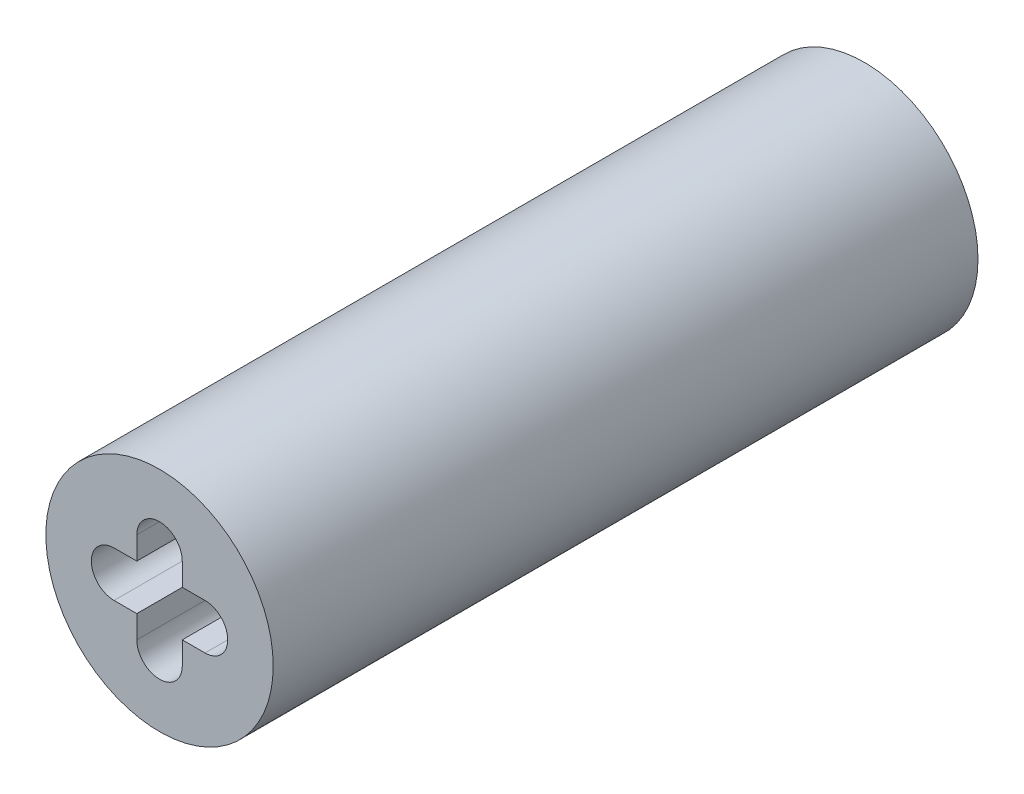
SolidWorks part; units mm, degrees
material "PVC Rigid"
ref_plane "Front Plane" through (0, 0, 0) normal (0, 0, 1) x (1, 0, 0)
ref_plane "Top Plane" through (0, 0, 0) normal (0, 1, 0) x (1, 0, 0)
ref_plane "Right Plane" through (0, 0, 0) normal (1, 0, 0) x (0, 0, -1)
sketch "Sketch1" plane through (0, 0, 0) normal (0, 0, 1) x (1, 0, 0)
  line L0 (0, 0) -> (3.048, 0) construction
  line L1 (0, 0.762) -> (3.048, 0.762)
  line L2 (0, -0.762) -> (3.048, -0.762)
  line L8 (1.524, 1.524) -> (1.524, -1.524) construction
  line L9 (2.286, 1.524) -> (2.286, -1.524)
  line L10 (0.762, 1.524) -> (0.762, -1.524)
  arc A0 (0, 0.762) -> (0, -0.762) centre (0, 0) ccw
  arc A2 (3.048, -0.762) -> (3.048, 0.762) centre (3.048, 0) ccw
  arc A4 (2.286, 1.524) -> (0.762, 1.524) centre (1.524, 1.524) ccw
  arc A5 (0.762, -1.524) -> (2.286, -1.524) centre (1.524, -1.524) ccw
  circle A7 centre (1.524, 0) radius 2.286 construction
  circle A8 centre (1.524, 0) radius 3.81
  point P1 (3.81, 0)
  point P3 (1.524, 0)
  point P8 (1.524, 0)
  point P13 (5.334, 0)
  point P15 (7.62, 0)
  point P17 (0, 3.302)
  point P18 (19.05, 3.302)
  point P19 (0, -3.302)
  point P20 (19.05, -3.302)
  point P23 (13.843, 0)
  point P24 (3.81, 0)
  point P25 (23.368, 0)
  point P26 (3.429, 0)
  point P27 (-7.874, -3.302)
  point P28 (7.874, -3.302)
  point P29 (-7.874, 3.302)
  point P30 (7.874, 3.302)
  point P35 (11.811, 0)
  point P60 (11.5175, 1.1139)
  dimension "D2" = 1.524
  dimension "D3" = 4.572
  dimension "D4" = 7.62
  dimension "D1" = 1.524
extrude "Boss-Extrude1" add sketch "Sketch1" along normal blind 23.622 contours A8 A5 L10 L2 A0 L1 A4 L9 A2 region at (-2.1782, 0, 0)
